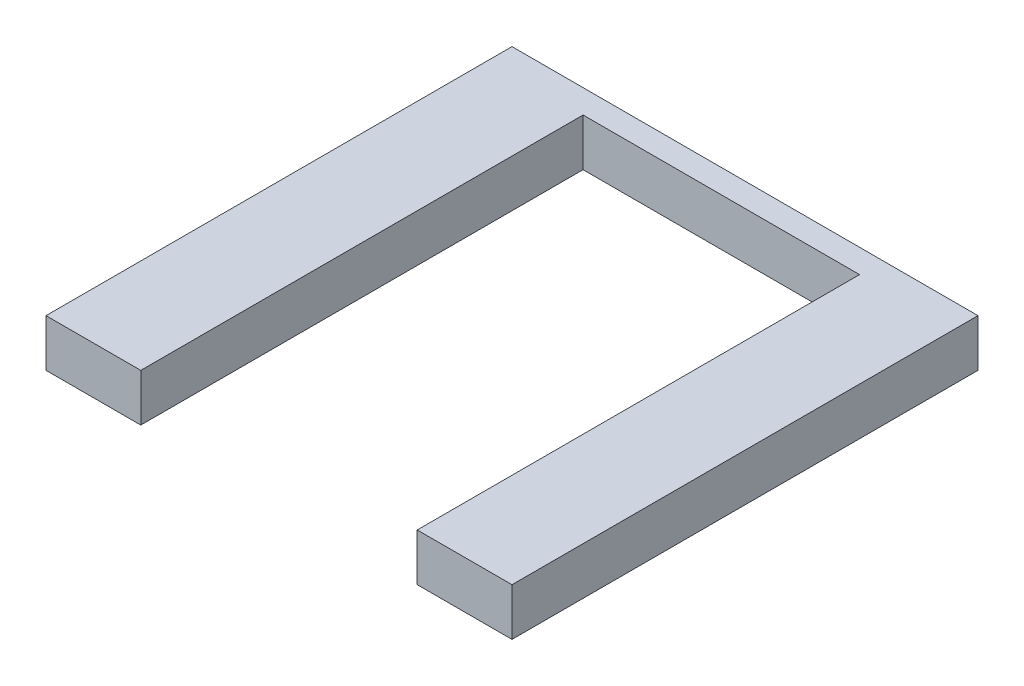
SolidWorks part; units mm, degrees
ref_plane "Front Plane" through (0, 0, 0) normal (0, 0, 1) x (1, 0, 0)
ref_plane "Top Plane" through (0, 0, 0) normal (0, 1, 0) x (1, 0, 0)
ref_plane "Right Plane" through (0, 0, 0) normal (1, 0, 0) x (0, 0, -1)
sketch "Sketch1" plane through (0, 0, 0) normal (0, 1, 0) x (1, 0, 0)
  line L1 (0, 0) -> (749.3, 0)
  line L2 (0, 0) -> (0, -749.3)
  line L3 (0, -749.3) -> (749.3, -749.3)
  line L4 (749.3, 0) -> (749.3, -749.3)
  dimension "D1" = 749.3
  dimension "D2" = 749.3
extrude "Boss-Extrude1" add sketch "Sketch1" along normal blind 76.2
sketch "Sketch2" plane through (0, 76.2, 0) normal (0, 1, 0) x (1, 0, 0)
  line L0 (0, -749.3) -> (749.3, -749.3) construction
  line L1 (152.4, -38.1) -> (596.9, -38.1)
  line L2 (152.4, -38.1) -> (152.4, -749.3)
  line L3 (152.4, -749.3) -> (596.9, -749.3)
  line L4 (596.9, -38.1) -> (596.9, -749.3)
  line L5 (0, 0) -> (0, -749.3) construction
  line L6 (749.3, -749.3) -> (749.3, 0) construction
  dimension "D1" = 711.2
  dimension "D2" = 152.4
  dimension "D3" = 152.4
extrude "Cut-Extrude1" cut sketch "Sketch2" against normal blind 76.2
